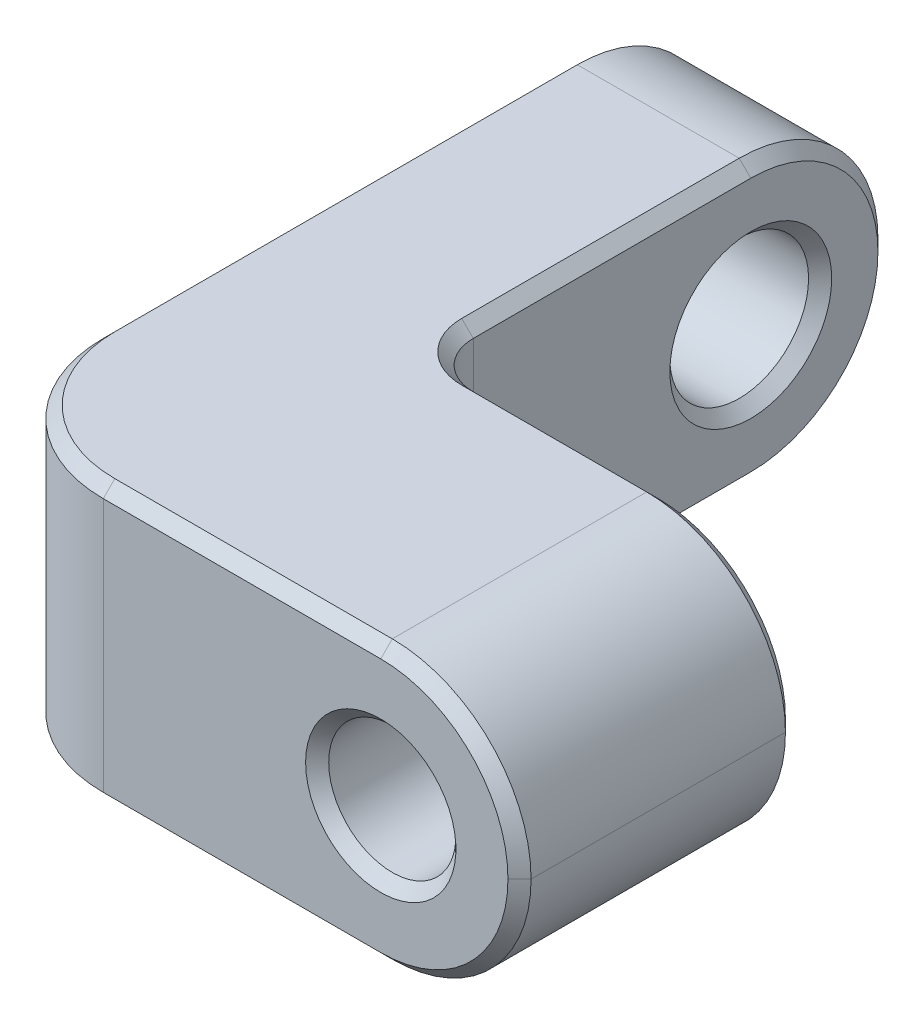
SolidWorks part; units mm, degrees
ref_plane "Front Plane" through (0, 0, 0) normal (0, 0, 1) x (1, 0, 0)
ref_plane "Top Plane" through (0, 0, 0) normal (0, 1, 0) x (1, 0, 0)
ref_plane "Right Plane" through (0, 0, 0) normal (1, 0, 0) x (0, 0, -1)
sketch "Sketch1" plane through (0, 0, 0) normal (0, 1, 0) x (1, 0, 0)
  line L0 (0, 0) -> (19.05, 0)
  line L1 (19.05, 0) -> (19.05, 9.525)
  line L2 (19.05, 9.525) -> (6.35, 9.525)
  line L3 (6.35, 9.525) -> (6.35, 25.4)
  line L4 (6.35, 25.4) -> (0, 25.4)
  line L5 (0, 25.4) -> (0, 0)
  dimension "D1" = 9.525
  dimension "D2" = 12.7
  dimension "D3" = 6.35
  dimension "D4" = 15.875
extrude "Boss-Extrude1" add sketch "Sketch1" along normal mid plane 9.525
sketch "Sketch2" plane through (0, 0, -9.525) normal (0, 0, -1) x (-1, 0, 0)
  line L0 (-19.05, 4.7625) -> (-19.05, -4.7625) construction
  circle A0 centre (-14.2875, 0) radius 2.1828
  dimension "D2" = 4.3656
  dimension "D1" = 4.7625
extrude "Cut-Extrude1" cut sketch "Sketch2" against normal through all both and the other way through all
sketch "Sketch3" plane through (6.35, 0, 0) normal (1, 0, 0) x (0, 0, -1)
  line L0 (25.4, 4.7625) -> (25.4, -4.7625) construction
  circle A0 centre (20.6375, 0) radius 2.3813
  point P4 (0, 0)
  dimension "D2" = 4.7625
  dimension "D1" = 4.7625
extrude "Cut-Extrude2" cut sketch "Sketch3" against normal through all both and the other way through all
fillet "Fillet1" radius 4.7625 5 edges at (0, 0, 0) (3.175, -4.7625, -25.4) (3.175, 4.7625, -25.4) (19.05, -4.7625, -4.7625) (19.05, 4.7625, -4.7625)
fillet "Fillet2" radius 1.5875 1 edges at (6.35, 0, -9.525)
chamfer "Chamfer1" distance 0.3969 angle 45 24 edges at (6.35, 0, -18.2563) (0, 0, -23.0187) (0, -3.3676, -24.0051) (0, 3.3676, -24.0051) (0, -4.7625, -12.7) (0, 4.7625, -12.7) (1.3949, -4.7625, -1.3949) (1.3949, 4.7625, -1.3949) (9.525, -4.7625, 0) (17.6551, -3.3676, 0) (17.6551, 3.3676, 0) (9.525, 4.7625, 0) (12.1047, 0, 0) (6.35, 3.3676, -24.0051) (6.35, -3.3676, -24.0051) (6.35, 4.7625, -15.875) (6.35, -4.7625, -15.875) (6.815, 4.7625, -9.99) (6.815, -4.7625, -9.99) (11.1125, 4.7625, -9.525) (17.6551, 3.3676, -9.525) (17.6551, -3.3676, -9.525) (11.1125, -4.7625, -9.525) (16.4703, 0, -9.525)
